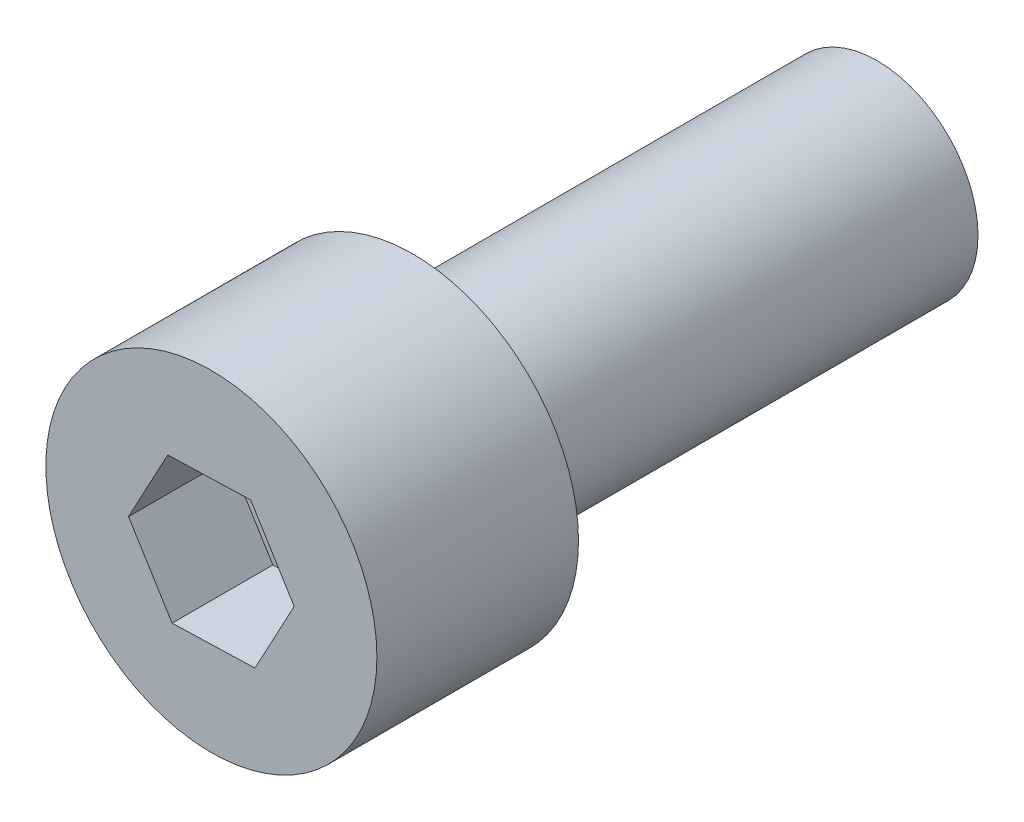
SolidWorks part; units mm, degrees
material "AISI Type A2 Tool Steel"
ref_plane "Front" through (0, 0, 0) normal (0, 0, 1) x (1, 0, 0)
ref_plane "Top" through (0, 0, 0) normal (0, 1, 0) x (1, 0, 0)
ref_plane "Right" through (0, 0, 0) normal (1, 0, 0) x (0, 0, -1)
sketch "Sketch1" plane through (0, 0, 0) normal (0, 0, 1) x (1, 0, 0)
  circle A0 centre (0, 0) radius 2.413
  dimension "D1" = 4.826
extrude "Boss-Extrude1" add sketch "Sketch1" along normal blind 11.1125
cosmetic thread "Cosmetic Thread1" parameters "D2"=3.8811
sketch "Sketch2" plane through (0, 0, 11.1125) normal (0, 0, 1) x (1, 0, 0)
  circle A0 centre (0, 0) radius 3.9624
  dimension "D1" = 7.9248
extrude "Boss-Extrude2" add sketch "Sketch2" along normal blind 4.826
sketch "Sketch3" plane through (0, 0, 15.9385) normal (0, 0, 1) x (1, 0, 0)
  line L1 (-1.9835, -0.0597) -> (-0.94, -1.7476)
  line L2 (-0.94, -1.7476) -> (1.0434, -1.6879)
  line L3 (1.0434, -1.6879) -> (1.9835, 0.0597)
  line L4 (1.9835, 0.0597) -> (0.94, 1.7476)
  line L5 (0.94, 1.7476) -> (-1.0434, 1.6879)
  line L6 (-1.0434, 1.6879) -> (-1.9835, -0.0597)
  circle A0 centre (0, 0) radius 1.9844
  circle A1 centre (0, 0) radius 1.7185 construction
  dimension "D1" = 3.9688
extrude "Cut-Extrude1" cut sketch "Sketch3" against normal blind 2.413 contours L5 L6 L1 L2 L3 L4 region at (0, 0, 15.9385)
